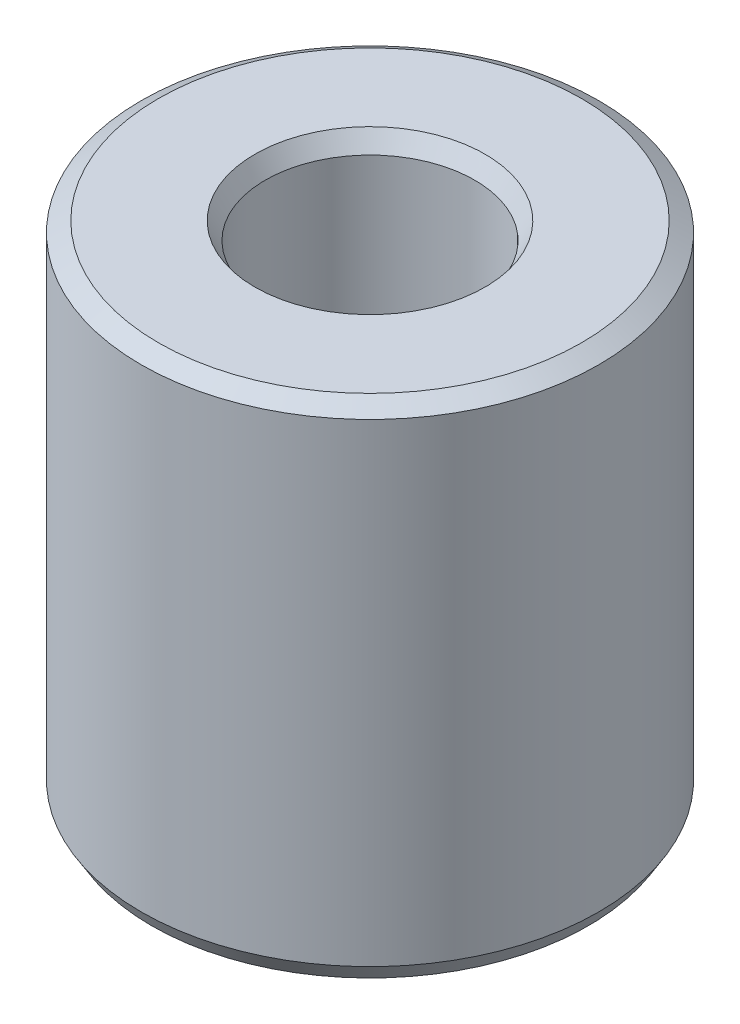
SolidWorks part; units mm, degrees
ref_plane "Front Plane" through (0, 0, 0) normal (0, 0, 1) x (1, 0, 0)
ref_plane "Top Plane" through (0, 0, 0) normal (0, 1, 0) x (1, 0, 0)
ref_plane "Right Plane" through (0, 0, 0) normal (1, 0, 0) x (0, 0, -1)
sketch "Sketch1" plane through (0, 0, 0) normal (0, 1, 0) x (1, 0, 0)
  circle A0 centre (0, 0) radius 27.5
  dimension "SLEEVE_OD" = 55
extrude "Boss-Extrude1" add sketch "Sketch1" along normal blind 60.2791
sketch "Sketch2" plane through (0, 0, 0) normal (0, 1, 0) x (1, 0, 0)
  circle A0 centre (0, 0) radius 12.5871
  dimension "BORE_D" = 25.1741
extrude "Cut-Extrude1" cut sketch "Sketch2" along normal through all
chamfer "Chamfer1" distance 1.2524 angle 58.824 4 edges at (0, 60.2791, 12.5871) (0, 0, 12.5871) (0, 0, 27.5) (0, 60.2791, 27.5) first distance on face at (0, 60.2791, 12.5871) first distance on face at (0, 0, 12.5871) first distance on face at (0, 60.2791, 27.5)
